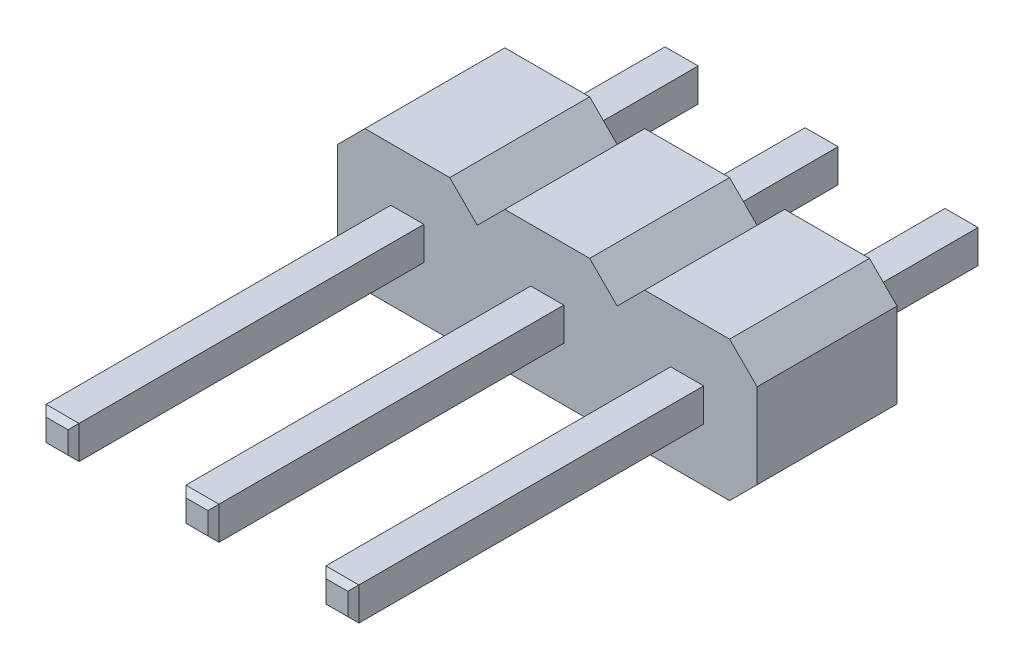
SolidWorks part; units mm, degrees
ref_plane "Front Plane" through (0, 0, 0) normal (0, 0, 1) x (1, 0, 0)
ref_plane "Top Plane" through (0, 0, 0) normal (0, 1, 0) x (1, 0, 0)
ref_plane "Right Plane" through (0, 0, 0) normal (1, 0, 0) x (0, 0, -1)
sketch "Sketch1" plane through (0, 0, 0) normal (0, 0, 1) x (1, 0, 0)
  line L0 (1.27, 0) -> (0, 0) construction
  line L5 (0, 0) -> (0, 1.27) construction
  line L6 (-0.77, 1.27) -> (0.77, 1.27)
  line L7 (0.77, 1.27) -> (1.27, 0.77)
  line L8 (1.27, 0.77) -> (1.27, -0.77)
  line L9 (-1.27, 0.77) -> (-1.27, -0.77)
  line L10 (-0.77, 1.27) -> (-1.27, 0.77)
  line L11 (0.77, -1.27) -> (1.27, -0.77)
  line L12 (-0.77, -1.27) -> (0.77, -1.27)
  line L13 (-0.77, -1.27) -> (-1.27, -0.77)
  point P13 (-1.27, 0)
  dimension "D1" = 1.27
  dimension "D2" = 45
  dimension "D3" = 0.5
extrude "Plastic" add sketch "Sketch1" along normal blind 2.54
sketch "Sketch2" plane through (0, 0, 0) normal (1, 0, 0) x (0, 0, -1)
  line L0 (-8.9, 0.3) -> (-8.9, -0.3)
  line L1 (-8.9, 0) -> (2.54, 0) construction
  line L4 (-8.9, -0.3) -> (2.54, -0.3)
  line L6 (-8.9, 0.3) -> (2.54, 0.3)
  line L8 (2.54, -0.3) -> (2.54, 0.3)
  line L11 (-9.5, 4.63) -> (-9.5, 0.6) construction
  line L12 (-9.8, 4.63) -> (-9.8, 0.6) construction
  line L13 (-9.2, 4.63) -> (-9.2, 0.6) construction
  arc A3 (-9.8, 0.6) -> (-8.9, -0.3) centre (-8.9, 0.6) ccw construction
  arc A4 (-9.5, 0.6) -> (-8.9, 0) centre (-8.9, 0.6) ccw construction
  arc A5 (-9.2, 0.6) -> (-8.9, 0.3) centre (-8.9, 0.6) ccw construction
  dimension "D1" = 8.9
  dimension "D4" = 2.54
  dimension "D2" = 0.3
  dimension "D3" = 0.3
extrude "Contact" add sketch "Sketch2" along normal mid plane 0.6
chamfer "Chamfer1" distance 0.1 angle 45 8 edges at (0.3, 0, -2.54) (0, -0.3, -2.54) (-0.3, 0, -2.54) (0, 0.3, -2.54) (-0.3, 0, 8.9) (0, 0.3, 8.9) (0.3, 0, 8.9) (0, -0.3, 8.9)
pattern_linear "Линейный массив1" count 3 spacing 2.54 along (1, 0, 0) of "Contact", "Plastic", "Chamfer1"
